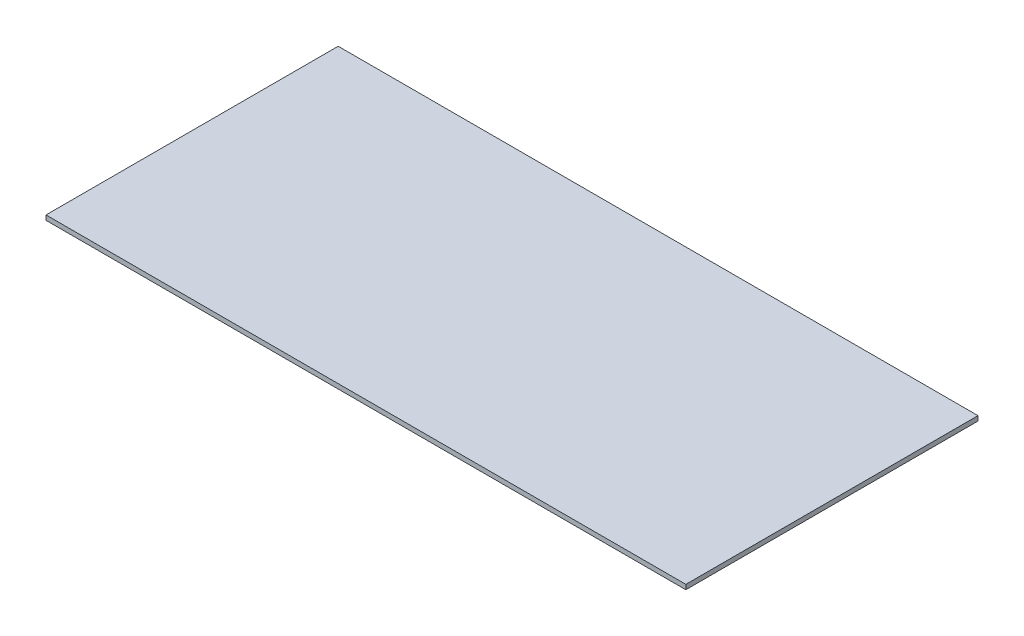
SolidWorks part; units mm, degrees
material "Mahogany"
ref_plane "Front Plane" through (0, 0, 0) normal (0, 0, 1) x (1, 0, 0)
ref_plane "Top Plane" through (0, 0, 0) normal (0, 1, 0) x (1, 0, 0)
ref_plane "Right Plane" through (0, 0, 0) normal (1, 0, 0) x (0, 0, -1)
sketch "Sketch1" plane through (0, 0, 0) normal (0, 1, 0) x (1, 0, 0)
  line L1 (865, -395) -> (-865, -395)
  line L2 (865, -395) -> (865, 395)
  line L3 (865, 395) -> (-865, 395)
  line L4 (-865, -395) -> (-865, 395)
  line L5 (865, -395) -> (-865, 395) construction
  line L6 (865, 395) -> (-865, -395) construction
  point P0 (0, 0)
  dimension "D1" = 1730
  dimension "D2" = 790
extrude "Boss-Extrude1" add sketch "Sketch1" along normal blind 12.7
equation "\"W\"= 1700"
equation "\"L\"= 760"
equation "\"H\"= 810"
equation "\"ARM_BOLT_SPACING\"= 140"
equation "\"ARM_TO_WALL\"= 300"
equation "\"D1@Sketch1\"=\"W\"+30"
equation "\"D2@Sketch1\"=\"L\"+30"
